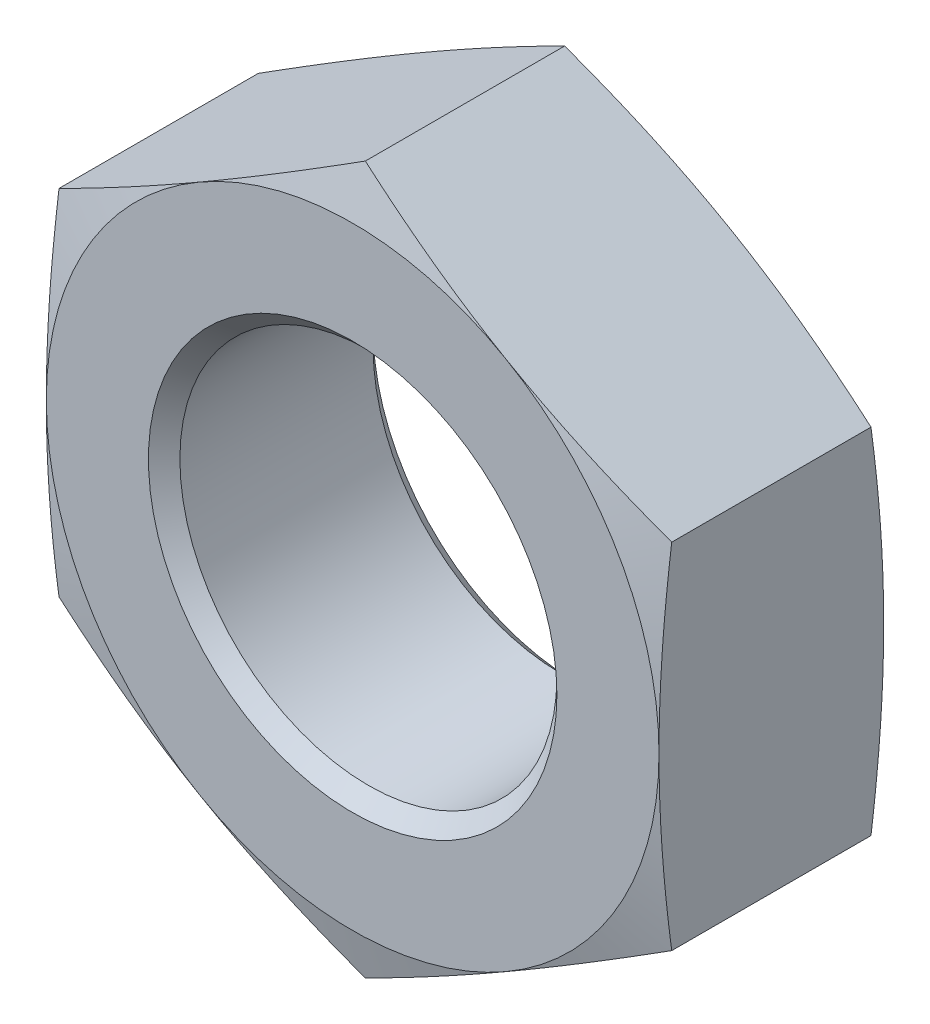
SolidWorks part; units mm, degrees
material "Cast Alloy Steel"
ref_plane "Front Plane" through (0, 0, 0) normal (0, 0, 1) x (1, 0, 0)
ref_plane "Top Plane" through (0, 0, 0) normal (0, 1, 0) x (1, 0, 0)
ref_plane "Right Plane" through (0, 0, 0) normal (1, 0, 0) x (0, 0, -1)
sketch "Sketch1" plane through (0, 0, 0) normal (1, 0, 0) x (0, 0, -1)
  line L0 (0, 0) -> (0, 19.05)
  line L1 (0, 19.05) -> (1.0209, 22.86)
  line L2 (1.0209, 22.86) -> (12.9491, 22.86)
  line L3 (12.9491, 22.86) -> (13.97, 19.05)
  line L4 (13.97, 19.05) -> (13.97, 0)
  line L5 (13.97, 0) -> (0, 0)
  line L6 (13.97, 0) -> (0, 0) construction
sketch "Sketch2" plane through (0, 0, 0) normal (0, 0, 1) x (1, 0, 0)
  line L0 (-38.1, 38.1) -> (-38.1, -38.1)
  line L1 (-38.1, -38.1) -> (38.1, -38.1)
  line L2 (38.1, -38.1) -> (38.1, 38.1)
  line L3 (38.1, 38.1) -> (-38.1, 38.1)
  line L4 (-19.05, 10.9985) -> (-19.05, -10.9985)
  line L5 (-19.05, -10.9985) -> (0, -21.997)
  line L6 (0, -21.997) -> (19.05, -10.9985)
  line L7 (19.05, -10.9985) -> (19.05, 10.9985)
  line L8 (19.05, 10.9985) -> (0, 21.997)
  line L9 (0, 21.997) -> (-19.05, 10.9985)
revolve "Revolve1" add sketch "Sketch1" angle 360 about L6 reverse direction yes
extrude "Cut-Extrude1" cut sketch "Sketch2" against normal blind 13.97
sketch "Sketch3" plane through (0, 0, 0) normal (1, 0, 0) x (0, 0, -1)
  line L0 (0, 0) -> (0, 12.7)
  line L1 (0, 12.7) -> (0.9779, 11.7221)
  line L2 (0.9779, 11.7221) -> (12.9921, 11.7221)
  line L3 (12.9921, 11.7221) -> (13.97, 12.7)
  line L4 (13.97, 12.7) -> (13.97, 0)
  line L5 (13.97, 0) -> (0, 0)
  line L6 (13.97, 0) -> (0, 0) construction
revolve "Cut-Revolve1" cut sketch "Sketch3" angle 360 about L6 reverse direction yes
cosmetic thread "Cosmetic Thread1" parameters "D1"=13.97, "D2"=25.4
ref_plane "NUT XY" through (0, 0, 0) normal (0, 0, 1) x (1, 0, 0)
ref_plane "NUT XZ" through (0, 0, 0) normal (0, -1, 0) x (-1, 0, 0)
ref_plane "NUT YZ" through (0, 0, 0) normal (1, 0, 0) x (0, 0, -1)
ref_axis "NUT X" through (-80.9, 0, 0) along (1, 0, 0)
ref_axis "NUT Y" through (0, -50, 0) along (0, 1, 0)
ref_axis "NUT Z" through (0, 0, 80.9) along (0, 0, -1)
sketch3d "NUT"
  point P0 (0, 0, 0)
ref_plane "a1 XY" through (0, 0, 0) normal (0, 0, 1) x (1, 0, 0)
ref_plane "a1 XZ" through (0, 19.05, 0) normal (0, -1, 0) x (-1, 0, 0)
ref_plane "a1 YZ" through (-19.05, 0, 0) normal (1, 0, 0) x (0, 0, -1)
ref_axis "a1 X" through (-80.9, 19.05, 0) along (1, 0, 0)
ref_axis "a1 Y" through (-19.05, -50, 0) along (0, 1, 0)
ref_axis "a1 Z" through (-19.05, 19.05, 80.9) along (0, 0, -1)
sketch3d "a1"
  point P0 (-19.05, 19.05, 0)
ref_plane "a2 XY" through (0, 0, 0) normal (0, 0, 1) x (1, 0, 0)
ref_plane "a2 XZ" through (0, 19.05, 0) normal (0, -1, 0) x (-1, 0, 0)
ref_plane "a2 YZ" through (19.05, 0, 0) normal (1, 0, 0) x (0, 0, -1)
ref_axis "a2 X" through (-80.9, 19.05, 0) along (1, 0, 0)
ref_axis "a2 Y" through (19.05, -50, 0) along (0, 1, 0)
ref_axis "a2 Z" through (19.05, 19.05, 80.9) along (0, 0, -1)
sketch3d "a2"
  point P0 (19.05, 19.05, 0)
ref_plane "b1 XY" through (0, 0, 0) normal (1, 0, 0) x (0, 0, -1)
ref_plane "b1 XZ" through (0, 19.05, 0) normal (0, -1, 0) x (-1, 0, 0)
ref_plane "b1 YZ" through (0, 0, 0) normal (0, 0, -1) x (-1, 0, 0)
ref_axis "b1 X" through (0, 19.05, 80.9) along (0, 0, -1)
ref_axis "b1 Y" through (0, -50, 0) along (0, 1, 0)
ref_axis "b1 Z" through (80.9, 19.05, 0) along (-1, 0, 0)
sketch3d "b1"
  point P0 (0, 19.05, 0)
ref_plane "b2 XY" through (0, 0, 0) normal (1, 0, 0) x (0, 0, -1)
ref_plane "b2 XZ" through (0, 19.05, 0) normal (0, -1, 0) x (-1, 0, 0)
ref_plane "b2 YZ" through (0, 0, -13.97) normal (0, 0, -1) x (-1, 0, 0)
ref_axis "b2 X" through (0, 19.05, 80.9) along (0, 0, -1)
ref_axis "b2 Y" through (0, -50, -13.97) along (0, 1, 0)
ref_axis "b2 Z" through (80.9, 19.05, -13.97) along (-1, 0, 0)
sketch3d "b2"
  point P0 (0, 19.05, -13.97)
ref_plane "e XY" through (0, 0, 0) normal (1, 0, 0) x (0, 0, -1)
ref_plane "e XZ" through (0, 0, 0) normal (0, -1, 0) x (-1, 0, 0)
ref_plane "e YZ" through (0, 0, -13.97) normal (0, 0, -1) x (-1, 0, 0)
ref_axis "e X" through (0, 0, 80.9) along (0, 0, -1)
ref_axis "e Y" through (0, -50, -13.97) along (0, 1, 0)
ref_axis "e Z" through (80.9, 0, -13.97) along (-1, 0, 0)
sketch3d "e"
  point P0 (0, 0, -13.97)
ref_plane "ol1 XY" through (0, 0, 0) normal (0, 1, 0) x (1, 0, 0)
ref_plane "ol1 XZ" through (0, 0, -19.05) normal (0, 0, 1) x (1, 0, 0)
ref_plane "ol1 YZ" through (0, 0, 0) normal (1, 0, 0) x (0, 0, -1)
ref_axis "ol1 X" through (-80.9, 0, -19.05) along (1, 0, 0)
ref_axis "ol1 Y" through (0, 0, 50) along (0, 0, -1)
ref_axis "ol1 Z" through (0, 50, -19.05) along (0, -1, 0)
sketch3d "ol1"
  point P0 (0, 0, -19.05)
ref_plane "ol2 XY" through (0, 0, 0) normal (0, 1, 0) x (1, 0, 0)
ref_plane "ol2 XZ" through (0, 0, -19.05) normal (0, 0, 1) x (1, 0, 0)
ref_plane "ol2 YZ" through (13.97, 0, 0) normal (1, 0, 0) x (0, 0, -1)
ref_axis "ol2 X" through (-80.9, 0, -19.05) along (1, 0, 0)
ref_axis "ol2 Y" through (13.97, 0, 50) along (0, 0, -1)
ref_axis "ol2 Z" through (13.97, 50, -19.05) along (0, -1, 0)
sketch3d "ol2"
  point P0 (13.97, 0, -19.05)
ref_plane "th1 XY" through (0, 0, 0) normal (1, 0, 0) x (0, 0, -1)
ref_plane "th1 XZ" through (0, 12.7, 0) normal (0, -1, 0) x (-1, 0, 0)
ref_plane "th1 YZ" through (0, 0, -13.97) normal (0, 0, -1) x (-1, 0, 0)
ref_axis "th1 X" through (0, 12.7, 80.9) along (0, 0, -1)
ref_axis "th1 Y" through (0, -50, -13.97) along (0, 1, 0)
ref_axis "th1 Z" through (80.9, 12.7, -13.97) along (-1, 0, 0)
sketch3d "th1"
  point P0 (0, 12.7, -13.97)
ref_plane "th2 XY" through (0, 0, 0) normal (1, 0, 0) x (0, 0, -1)
ref_plane "th2 XZ" through (0, -12.7, 0) normal (0, -1, 0) x (-1, 0, 0)
ref_plane "th2 YZ" through (0, 0, -13.97) normal (0, 0, -1) x (-1, 0, 0)
ref_axis "th2 X" through (0, -12.7, 80.9) along (0, 0, -1)
ref_axis "th2 Y" through (0, -50, -13.97) along (0, 1, 0)
ref_axis "th2 Z" through (80.9, -12.7, -13.97) along (-1, 0, 0)
sketch3d "th2"
  point P0 (0, -12.7, -13.97)
